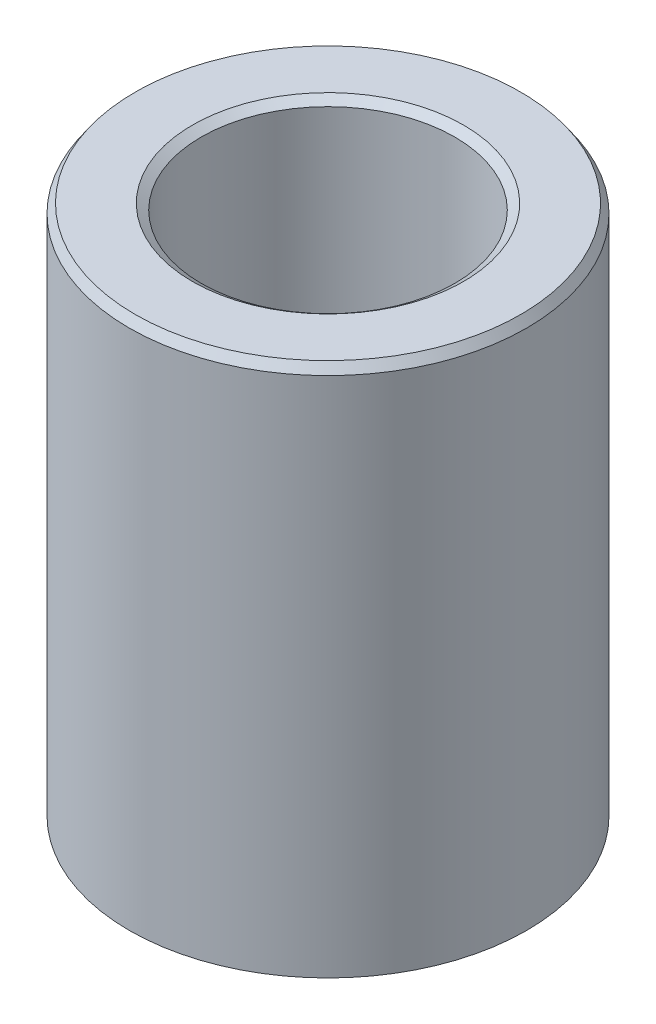
SolidWorks part; units mm, degrees
ref_plane "Front Plane" through (0, 0, 0) normal (0, 0, 1) x (1, 0, 0)
ref_plane "Top Plane" through (0, 0, 0) normal (0, 1, 0) x (1, 0, 0)
ref_plane "Right Plane" through (0, 0, 0) normal (1, 0, 0) x (0, 0, -1)
sketch "Sketch1" plane through (0, 0, 0) normal (0, 1, 0) x (1, 0, 0)
  circle A0 centre (0, 0) radius 47.5
  dimension "SLEEVE_OD" = 95
extrude "Boss-Extrude1" add sketch "Sketch1" along normal blind 128.2294
sketch "Sketch2" plane through (0, 0, 0) normal (0, 1, 0) x (1, 0, 0)
  circle A0 centre (0, 0) radius 30.3147
  dimension "BORE_D" = 60.6294
extrude "Cut-Extrude1" cut sketch "Sketch2" along normal through all
chamfer "Chamfer1" distance 2.0909 angle 34.36 4 edges at (0, 128.2294, 30.3147) (0, 0, 30.3147) (0, 0, 47.5) (0, 128.2294, 47.5) first distance on face at (0, 128.2294, 30.3147) first distance on face at (0, 0, 30.3147) first distance on face at (0, 128.2294, 47.5)
